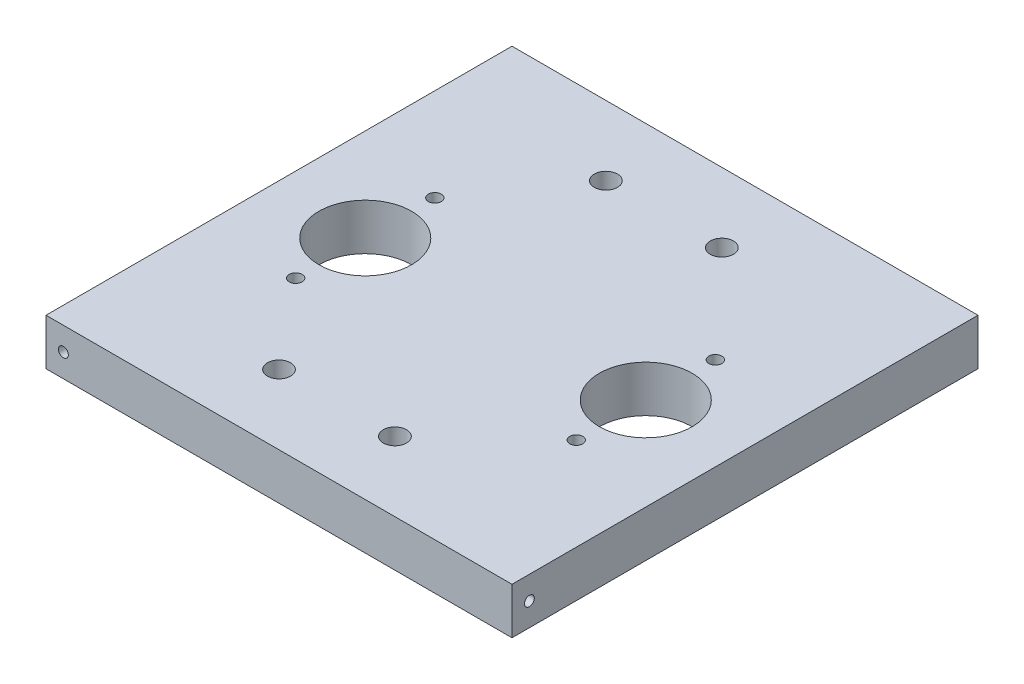
SolidWorks part; units mm, degrees
material "6061-T6 (SS)"
ref_plane "Front" through (0, 0, 0) normal (0, 0, 1) x (1, 0, 0)
ref_plane "Top" through (0, 0, 0) normal (0, 1, 0) x (1, 0, 0)
ref_plane "Right" through (0, 0, 0) normal (1, 0, 0) x (0, 0, -1)
sketch "Sketch1" plane through (0, 0, 0) normal (0, 1, 0) x (1, 0, 0)
  line L1 (0, 0) -> (127.635, 0)
  line L2 (0, 0) -> (0, 127.635)
  line L3 (0, 127.635) -> (127.635, 127.635)
  line L4 (127.635, 0) -> (127.635, 127.635)
  dimension "D1" = 127.635
  dimension "D2" = 127.635
extrude "Main Plate" add sketch "Sketch1" along normal blind 12.7
sketch "Sketch2" plane through (0, 12.7, 0) normal (0, 1, 0) x (1, 0, 0)
  line L0 (0, 127.635) -> (0, 0) construction
  line L1 (127.635, 127.635) -> (0, 127.635) construction
  circle A0 centre (44.7675, 108.585) radius 3.175
  dimension "D1" = 6.35
  dimension "D2" = 44.7675
  dimension "D3" = 19.05
extrude "U-Bolt Hole" cut sketch "Sketch2" against normal blind 12.7
pattern_linear "U-Bolt Pattern" count 2 spacing 31.75 along (1, 0, 0) count 2 spacing 89.535 along (0, 0, 1) of "U-Bolt Hole"
sketch "Sketch3" plane through (0, 12.7, 0) normal (0, 1, 0) x (1, 0, 0)
  line L0 (0, 127.635) -> (0, 0) construction
  line L1 (0, 0) -> (127.635, 0) construction
  circle A0 centre (25.4, 42.9895) radius 1.778
  dimension "D1" = 3.556
  dimension "D2" = 25.4
  dimension "D3" = 42.9895
extrude "Raptor Bolt Hole" cut sketch "Sketch3" against normal blind 12.7
pattern_linear "Raptor Bolt Pattern" count 2 spacing 38.1 along (0, 0, -1) count 2 spacing 76.835 along (1, 0, 0) of "Raptor Bolt Hole"
sketch "Sketch4" plane through (0, 12.7, 0) normal (0, 1, 0) x (1, 0, 0)
  line L0 (0, 127.635) -> (0, 0) construction
  circle A0 centre (25.4, 62.0395) radius 12.7
  dimension "D1" = 25.4
  dimension "D2" = 19.05
  dimension "D3" = 25.4
extrude "Co2 Cylinder Hole" cut sketch "Sketch4" against normal blind 12.7
pattern_linear "Co2 Pattern" count 2 spacing 76.835 along (1, 0, 0) of "Co2 Cylinder Hole"
sketch "Sketch5" plane through (0, 0, 0) normal (0, 0, 1) x (1, 0, 0)
  line L0 (0, 12.7) -> (0, 0) construction
  line L1 (0, 0) -> (127.635, 0) construction
  circle A0 centre (4.7625, 6.35) radius 1.3526
  dimension "D1" = 2.7051
  dimension "D2" = 4.7625
  dimension "D3" = 6.35
extrude "Frame attachment hole 1" cut sketch "Sketch5" against normal blind 12.7
sketch "Sketch6" plane through (0, 0, 0) normal (-1, 0, 0) x (0, 0, 1)
  line L2 (-127.635, 0) -> (0, 0) construction
  line L3 (-127.635, 12.7) -> (-127.635, 0) construction
  circle A0 centre (-122.8725, 6.35) radius 1.3525
  dimension "D1" = 2.7051
  dimension "D2" = 6.35
  dimension "D3" = 4.7625
extrude "Frame attachment hole 2" cut sketch "Sketch6" against normal blind 12.7
sketch "Sketch7" plane through (0, 0, -127.635) normal (0, 0, -1) x (-1, 0, 0)
  line L2 (-127.635, 0) -> (0, 0) construction
  line L3 (-127.635, 12.7) -> (-127.635, 0) construction
  circle A0 centre (-122.8725, 6.35) radius 1.3525
  dimension "D1" = 2.7051
  dimension "D2" = 6.35
  dimension "D3" = 4.7625
extrude "Frame attachment hole 3" cut sketch "Sketch7" against normal blind 12.7
sketch "Sketch8" plane through (127.635, 0, 0) normal (1, 0, 0) x (0, 0, -1)
  line L2 (0, 0) -> (127.635, 0) construction
  line L3 (0, 12.7) -> (0, 0) construction
  circle A0 centre (4.7625, 6.35) radius 1.3526
  dimension "D1" = 2.7051
  dimension "D2" = 6.35
  dimension "D3" = 4.7625
extrude "Frame attachment hole 4" cut sketch "Sketch8" against normal blind 12.7
